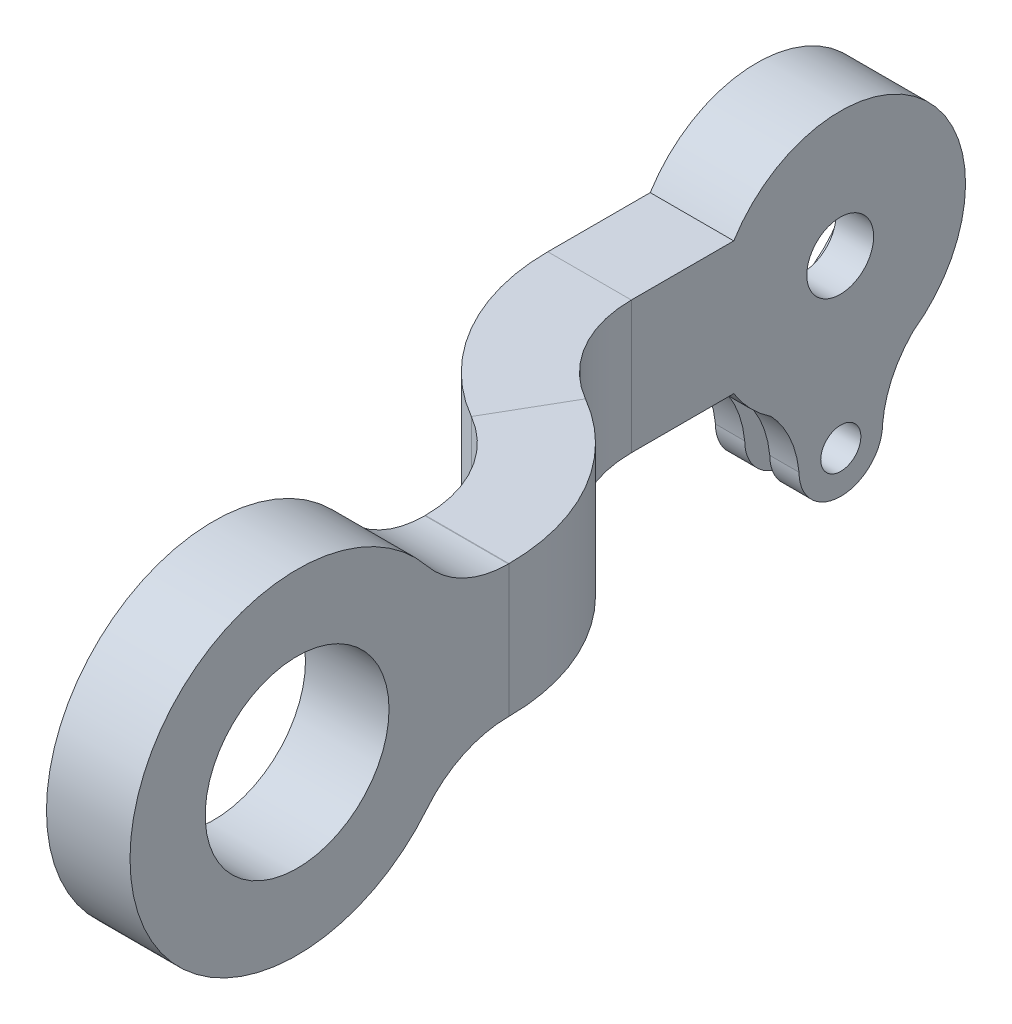
SolidWorks part; units mm, degrees
material "Resina de melamina"
ref_plane "Alzado" through (0, 0, 0) normal (0, 0, 1) x (1, 0, 0)
ref_plane "Planta" through (0, 0, 0) normal (0, 1, 0) x (1, 0, 0)
ref_plane "Vista lateral" through (0, 0, 0) normal (1, 0, 0) x (0, 0, -1)
sketch "Croquis1" plane through (0, 0, 0) normal (0, 1, 0) x (1, 0, 0)
  line L0 (0, 0) -> (0, 60) construction
  line L1 (0, 60) -> (-20, 60) construction
  line L2 (-20, 60) -> (-20, 85) construction
  line L3 (0, 15) -> (-20, 25.359) construction
  line L4 (-20, 85) -> (-20, 60)
  line L5 (0, 25.359) -> (0, 0)
  arc A0 (-20, 60) -> (-10, 42.6795) centre (0, 60) ccw
  arc A1 (0, 25.359) -> (-10, 42.6795) centre (-20, 25.359) ccw
  dimension "D4" = 20
  dimension "D1" = 60
  dimension "D2" = 25
  dimension "D3" = 20
sketch "Croquis2" plane through (0, 0, 0) normal (0, 0, 1) x (1, 0, 0)
  line L1 (5, -7.9175) -> (-5, -7.9175)
  line L2 (5, -7.9175) -> (5, 7.9175)
  line L3 (5, 7.9175) -> (-5, 7.9175)
  line L4 (-5, -7.9175) -> (-5, 7.9175)
  line L5 (5, -7.9175) -> (-5, 7.9175) construction
  line L6 (5, 7.9175) -> (-5, -7.9175) construction
  point P0 (0, 0)
  dimension "D1" = 10
sweep "Barrer1" add profiles "Croquis2" path "Croquis1"
sketch "Croquis4" plane through (-15, 0, 0) normal (1, 0, 0) x (0, 0, -1)
  line L1 (85, -7.9175) -> (85, 7.9175) construction
  circle A0 centre (85, 0) radius 15
  dimension "D2" = 30
extrude "Saliente-Extruir1" add sketch "Croquis4" against normal blind 10
sketch "Croquis5" plane through (5, 0, 0) normal (1, 0, 0) x (0, 0, -1)
  circle A0 centre (0, 0) radius 20
  dimension "D1" = 40
extrude "Saliente-Extruir2" add sketch "Croquis5" against normal blind 10
sketch "Croquis6" plane through (-15, 0, 0) normal (1, 0, 0) x (0, 0, -1)
  line L0 (60, 0) -> (85, 0) construction
  circle A0 centre (85, 0) radius 4
  dimension "D1" = 8
sketch "Croquis7" plane through (5, 0, 0) normal (1, 0, 0) x (0, 0, -1)
  circle A0 centre (0, 0) radius 11
  dimension "D1" = 22
ref_plane "Plano1" through (-15, 0, 0) normal (1, 0, 0) x (0, 0, -1)
sketch "Croquis12" plane through (-15, 0, 0) normal (1, 0, 0) x (0, 0, -1)
  line L0 (85.0685, -0.0274) -> (85.0685, 24.9726) construction
  line L1 (85.0685, 24.9726) -> (85.0685, 19.9726) construction
  line L2 (85.0685, 24.9726) -> (85.0685, 14.9726) construction
  arc A0 (90.0685, 19.9726) -> (80.0685, 19.9726) centre (85.0685, 19.9726) ccw
  arc A1 (94.2885, 11.6439) -> (75.8485, 11.6439) centre (85.0685, -0.0274) ccw
  spline S0 degree 2 poles (80.0685, 19.9726) (79.5667, 15.0283) (75.8485, 11.6439) knots 0 0 0 1 1 1
  spline S1 degree 2 poles (90.0685, 19.9726) (90.5703, 15.0283) (94.2885, 11.6439) knots 0 0 0 1 1 1
  dimension "D1" = 25
  dimension "D2" = 5
extrude "Saliente-Extruir5" add sketch "Croquis12" against normal blind 3.5
ref_plane "Plano2" through (-20, 0, 0) normal (1, 0, 0) x (0, 0, -1)
mirror "Simetría1" about plane through (-20, 0, 0) normal (1, 0, 0) of "Saliente-Extruir5"
sketch "Croquis13" plane through (-15, 0, 0) normal (1, 0, 0) x (0, 0, -1)
  circle A0 centre (85.0685, 19.9726) radius 2.5
  dimension "D1" = 5
extrude "Cortar-Extruir1" cut sketch "Croquis13" against normal blind 10
mirror "Simetría3" about plane through (0, 0, 0) normal (0, 1, 0) of "Simetría1"
sketch "Croquis20" plane through (-15, 0, 0) normal (1, 0, 0) x (0, 0, -1)
  line L0 (60, 0) -> (85, 0) construction
  line L2 (75.9168, 25.7358) -> (95.1724, 25.7358)
  line L3 (75.9168, 25.7358) -> (75.9168, 11.9372)
  line L5 (95.1724, 25.7358) -> (95.1724, 11.0237)
  arc A0 (95.1724, 11.0237) -> (75.9168, 11.9372) centre (85, 0) ccw
extrude "Cortar-Extruir5" cut sketch "Croquis20" against normal blind 10
sketch "Croquis21" plane through (-25, 0, 0) normal (-1, 0, 0) x (0, 0, 1)
  circle A0 centre (-85.0685, -19.9726) radius 2.4
  dimension "D1" = 4.8
extrude "Cortar-Extruir6" cut sketch "Croquis21" against normal blind 10
extrude "Cortar-Extruir7" cut sketch "Croquis7" against normal blind 10
fillet "Redondeo1" radius 12.5 1 edges at (0, -7.9175, -18.3661) type face fillet first side face at (0, 0, 0.8169) second side face at (0, -7.9175, -21.8625)
fillet "Redondeo2" radius 12.5 1 edges at (0, 7.9175, -18.3661) type face fillet first side face at (0, 0.1953, 1.4258) second side face at (0, 7.9175, -21.8625)
sketch "Croquis22" plane through (-25, 0, 0) normal (-1, 0, 0) x (0, 0, 1)
  circle A0 centre (-85, 0) radius 11.5
  dimension "D1" = 23
extrude "Cortar-Extruir8" cut sketch "Croquis22" against normal blind 5.5
extrude "Cortar-Extruir9" cut sketch "Croquis6" against normal blind 5.5
equation "\"3.5.00mm\"=3"
